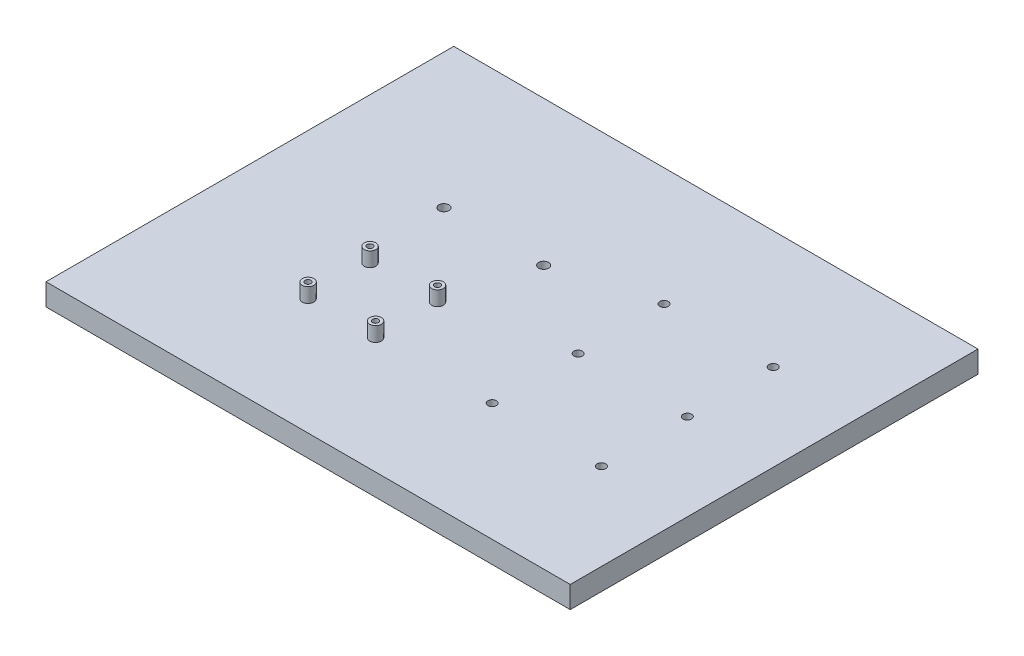
SolidWorks part; units mm, degrees
ref_plane "Front Plane" through (0, 0, 0) normal (0, 0, 1) x (1, 0, 0)
ref_plane "Top Plane" through (0, 0, 0) normal (0, 1, 0) x (1, 0, 0)
ref_plane "Right Plane" through (0, 0, 0) normal (1, 0, 0) x (0, 0, -1)
sketch "Sketch1" plane through (0, 0, 0) normal (0, 1, 0) x (1, 0, 0)
  line L1 (0, 0) -> (360, 0)
  line L2 (0, 0) -> (0, 280)
  line L3 (0, 280) -> (360, 280)
  line L4 (360, 0) -> (360, 280)
extrude "Boss-Extrude1" add sketch "Sketch1" along normal blind 10
sketch "Sketch2" plane through (0, 10, 0) normal (0, 1, 0) x (1, 0, 0)
  circle A0 centre (300.3952, 140) radius 2.925
  circle A1 centre (300.3952, 199) radius 2.925
  circle A2 centre (300.3952, 81) radius 2.925
  circle A3 centre (225.3952, 81) radius 2.925
  circle A4 centre (225.3952, 140) radius 2.925
  circle A5 centre (225.3952, 199) radius 2.925
  circle A6 centre (161.0805, 180.6564) radius 3.45
  circle A7 centre (92.5805, 180.6564) radius 3.45
  line M1 (0, 280) -> (0, 0)
  line M2 (0, 0) -> (360, 0)
  line M3 (360, 0) -> (360, 280)
  line M4 (360, 280) -> (0, 280)
extrude "Boss-Extrude3" add sketch "Sketch2" along normal blind 5 contours A4 A3 A0 A1 A2 A5 M4 M1 M2 M3 region at (179.9066, 10, -139.9698)
sketch "Sketch3" plane through (0, 15, 0) normal (0, 1, 0) x (1, 0, 0)
  circle A0 centre (100.078, 79.8812) radius 2
  circle A1 centre (146.433, 79.8812) radius 2
  circle A2 centre (146.433, 122.4262) radius 2
  circle A3 centre (100.078, 122.4262) radius 2
  circle A4 centre (100.078, 79.8812) radius 4
  circle A5 centre (100.078, 122.4262) radius 4
  circle A6 centre (146.433, 122.4262) radius 4
  circle A8 centre (146.433, 79.8812) radius 4
extrude "Boss-Extrude4" add sketch "Sketch3" along normal blind 10
